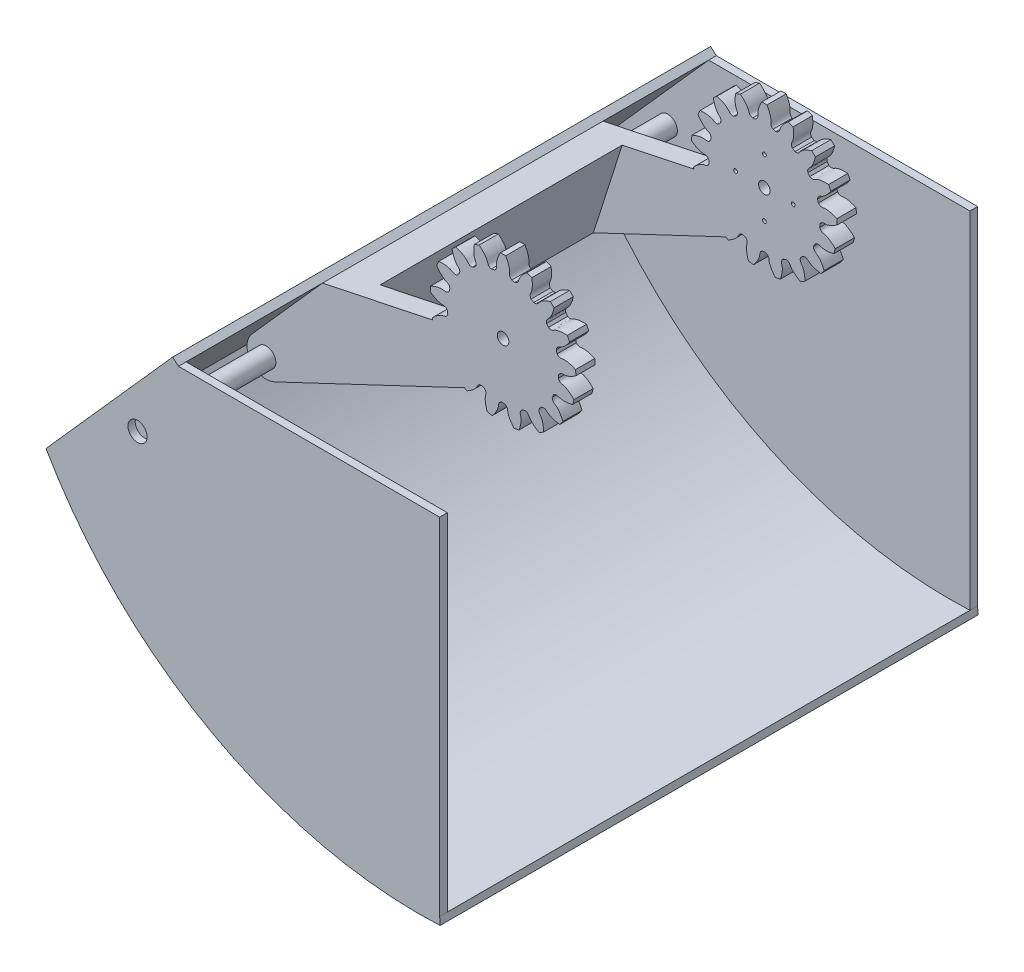
SolidWorks part; units mm, degrees
note: '?' marks a value the reader was unsure of.
ref_plane "前视基准面" through (0, 0, 0) normal (0, 0, 1) x (1, 0, 0)
ref_plane "上视基准面" through (0, 0, 0) normal (0, 1, 0) x (1, 0, 0)
ref_plane "右视基准面" through (0, 0, 0) normal (1, 0, 0) x (0, 0, -1)
sketch "草图1" plane through (0, 0, 0) normal (0, 0, 1) x (1, 0, 0)
  circle A0 centre (0, 0) radius 19
extrude "凸台-拉伸1" add sketch "草图1" along normal blind 5
ref_axis "基准轴1" through (0, 0, -1.5) along (0, 0, 1)?
sketch "草图2" plane through (0, 0, 0) normal (0, 0, 1) x (1, 0, 0)
  line L0 (0, 0) -> (0, 19) construction
  circle A0 centre (0, 0) radius 19 construction
  arc A1 (-2.2668, 14.3217) -> (-3.0598, 14.1735) centre (0, 0) ccw
  arc A2 (2.1781, 22.2607) -> (-10.0723, 19.9707) centre (0, 0) ccw
  spline S0 degree 3 poles (-2.2668, 14.3217) (-1.4942, 14.8276) (-1.7367, 15.4536) (-1.7089, 16.0896) (-1.7054, 16.1438) (-1.7004, 16.2043) (-1.6935, 16.271) (-1.6844, 16.344) (-1.673, 16.423) (-1.659, 16.5081) (-1.6421, 16.5993) (-1.6221, 16.6963) (-1.5988, 16.7991) (-1.5719, 16.9076) (-1.5411, 17.0218) (-1.5063, 17.1414) (-1.4672, 17.2665) (-1.4236, 17.3967) (-1.3753, 17.5321) (-1.3219, 17.6725) (-1.2634, 17.8177) (-1.1995, 17.9676) (-1.13, 18.1221) (-1.0547, 18.2808) (-0.9733, 18.4438) (-0.8858, 18.6107) (-0.7918, 18.7815) (-0.6913, 18.9559) (-0.584, 19.1337) (-0.4697, 19.3147) (-0.3483, 19.4988) (-0.2197, 19.6856) (-0.0836, 19.875) (0.0601, 20.0668) (0.2115, 20.2607) (0.3708, 20.4565) (0.5381, 20.654) (0.7135, 20.8528) (0.8973, 21.0529) (1.0893, 21.2538) (1.2899, 21.4553) (1.4991, 21.6573) (1.7927, 21.9296) (2.0214, 22.1293) (2.1781, 22.2607) knots 0 0 0 0 0.193883 0.199024 0.204851 0.211363 0.21856 0.226443 0.235011 0.244265 0.254205 0.264829 0.27614 0.288136 0.300817 0.314184 0.328236 0.342973 0.358397 0.374505 0.391299 0.408779 0.426944 0.445795 0.465331 0.485552 0.506459 0.528051 0.550329 0.573293 0.596941 0.621276 0.646296 0.672001 0.698392 0.725468 0.753229 0.781677 0.810809 0.840627 0.871131 0.90232 0.934195 1 1 1 1
  spline S1 degree 3 poles (-3.0598, 14.1735) (-3.9629, 14.3661) (-3.9629, 15.0375) (-4.2186, 15.6205) (-4.2414, 15.6698) (-4.268, 15.7243) (-4.2985, 15.7841) (-4.3333, 15.8488) (-4.3725, 15.9184) (-4.4163, 15.9927) (-4.465, 16.0716) (-4.5186, 16.1548) (-4.5776, 16.2423) (-4.6419, 16.3338) (-4.7118, 16.4291) (-4.7874, 16.5281) (-4.8691, 16.6306) (-4.9568, 16.7363) (-5.0508, 16.8451) (-5.1512, 16.9567) (-5.2583, 17.071) (-5.372, 17.1877) (-5.4926, 17.3066) (-5.6202, 17.4274) (-5.7549, 17.55) (-5.8969, 17.674) (-6.0462, 17.7993) (-6.2029, 17.9256) (-6.3672, 18.0526) (-6.5391, 18.1802) (-6.7188, 18.3079) (-6.9062, 18.4357) (-7.1016, 18.5632) (-7.3048, 18.6901) (-7.5161, 18.8162) (-7.7353, 18.9413) (-7.9627, 19.0649) (-8.1981, 19.187) (-8.4417, 19.3071) (-8.6934, 19.4251) (-8.9532, 19.5406) (-9.2212, 19.6534) (-9.5934, 19.8013) (-9.8788, 19.9048) (-10.0723, 19.9707) knots 0 0 0 0 0.193883 0.199024 0.204851 0.211363 0.21856 0.226443 0.235011 0.244265 0.254205 0.264829 0.27614 0.288136 0.300817 0.314184 0.328236 0.342973 0.358397 0.374505 0.391299 0.408779 0.426944 0.445795 0.465331 0.485552 0.506459 0.528051 0.550329 0.573293 0.596941 0.621276 0.646296 0.672001 0.698392 0.725468 0.753229 0.781677 0.810809 0.840627 0.871131 0.90232 0.934195 1 1 1 1
extrude "切除-拉伸1" cut sketch "草图2" along normal through all
pattern_circular "阵列(圆周)1" count 17 over 360 about axis through (0, 0, -1.5) along (0, 0, 1) of "切除-拉伸1"
sketch "草图3" plane through (0, 0, 0) normal (0, 0, 1) x (1, 0, 0)
  circle A0 centre (0, 0) radius 17 construction
  dimension "Dn" = 34
sketch "草图4" plane through (0, 0, 5) normal (0, 0, 1) x (1, 0, 0)
  circle A0 centre (0, 0) radius 1.5
  dimension "D1" = 3
extrude "切除-拉伸2" cut sketch "草图4" against normal up to next
sketch "草图5" plane through (0, 0, 5) normal (0, 0, 1) x (1, 0, 0)
  line L0 (-18.3355, -4.981) -> (-47, -11)
  line L1 (-47, -11) -> (-81.6624, -50)
  line L2 (-81.6624, -50) -> (-10.0568, -16.1202)
  line L3 (0, 0) -> (0, 43.3356) construction
  line L4 (-47, -11) -> (-47, -47.1311) construction
  arc A0 (-18.447, -4.5505) -> (-18.0795, -5.8421) centre (0, 0) ccw construction
  arc A1 (-18.3355, -4.981) -> (-18.0795, -5.8421) centre (0, 0) ccw
  arc A34 (-7.2873, 12.5358) -> (-7.9732, 12.1111) centre (0, 0) ccw
  arc A35 (-12.296, 14.4848) -> (-13.2884, 13.5801) centre (0, 0) ccw
  arc A36 (-11.3236, 9.0568) -> (-11.8098, 8.413) centre (0, 0) ccw
  arc A37 (-16.6982, 9.0649) -> (-17.2967, 7.8628) centre (0, 0) ccw
  arc A38 (-13.8307, 4.3546) -> (-14.0515, 3.5786) centre (0, 0) ccw
  arc A39 (-18.8452, 2.4207) -> (-18.9691, 1.0835) centre (0, 0) ccw
  arc A40 (-14.4698, -0.9356) -> (-14.3953, -1.739) centre (0, 0) ccw
  arc A41 (-18.447, -4.5505) -> (-18.0795, -5.8421) centre (0, 0) ccw
  arc A42 (-13.1547, -6.0996) -> (-12.7951, -6.8217) centre (0, 0) ccw
  arc A43 (-15.5575, -10.907) -> (-14.7483, -11.9787) centre (0, 0) ccw
  arc A44 (-10.063, -10.4397) -> (-9.4667, -10.9832) centre (0, 0) ccw
  arc A45 (-10.5669, -15.7905) -> (-9.4252, -16.4975) centre (0, 0) ccw
  arc A46 (-5.6122, -13.3699) -> (-4.8599, -13.6613) centre (0, 0) ccw
  arc A47 (-4.1491, -18.5414) -> (-2.8291, -18.7882) centre (0, 0) ccw
  arc A48 (-0.4034, -14.4944) -> (0.4033, -14.4944) centre (0, 0) ccw
  arc A49 (2.829, -18.7882) -> (4.149, -18.5415) centre (0, 0) ccw
  arc A50 (4.8598, -13.6614) -> (5.6121, -13.3699) centre (0, 0) ccw
  arc A51 (9.425, -16.4975) -> (10.5668, -15.7906) centre (0, 0) ccw
  arc A52 (9.4667, -10.9833) -> (10.0629, -10.4398) centre (0, 0) ccw
  arc A53 (14.7482, -11.9788) -> (15.5574, -10.9071) centre (0, 0) ccw
  arc A54 (12.795, -6.8219) -> (13.1546, -6.0997) centre (0, 0) ccw
  arc A55 (18.0795, -5.8422) -> (18.447, -4.5506) centre (0, 0) ccw
  arc A56 (14.3953, -1.7391) -> (14.4698, -0.9358) centre (0, 0) ccw
  arc A57 (18.9691, 1.0833) -> (18.8452, 2.4205) centre (0, 0) ccw
  arc A58 (14.0515, 3.5785) -> (13.8307, 4.3545) centre (0, 0) ccw
  arc A59 (17.2968, 7.8626) -> (16.6982, 9.0647) centre (0, 0) ccw
  arc A60 (11.8099, 8.4129) -> (11.3237, 9.0567) centre (0, 0) ccw
  arc A61 (13.2885, 13.58) -> (12.2961, 14.4847) centre (0, 0) ccw
  arc A62 (7.9733, 12.111) -> (7.2874, 12.5357) centre (0, 0) ccw
  arc A63 (7.4855, 17.4633) -> (6.2333, 17.9484) centre (0, 0) ccw
  arc A64 (3.0599, 14.1735) -> (2.2669, 14.3217) centre (0, 0) ccw
  arc A65 (0.6715, 18.9881) -> (-0.6714, 18.9881) centre (0, 0) ccw
  arc A66 (-2.2668, 14.3217) -> (-3.0598, 14.1735) centre (0, 0) ccw
  arc A67 (-6.2331, 17.9485) -> (-7.4853, 17.4634) centre (0, 0) ccw
  arc A76 (-13.1547, -6.0996) -> (-12.7951, -6.8217) centre (0, 0) ccw
  arc A77 (-15.5575, -10.907) -> (-14.7483, -11.9787) centre (0, 0) ccw
  arc A78 (-10.063, -10.4397) -> (-9.4667, -10.9832) centre (0, 0) ccw
  arc A79 (-10.5669, -15.7905) -> (-10.0568, -16.1202) centre (0, 0) ccw
  spline S36 degree 3 poles (677.1036, 740.5769) (-18.0035, -11.038) (-5.5387, 8.9839) (-9.5908, 13.056) (-9.6465, 13.1087) (-9.7101, 13.1654) (-9.7659, 13.2132) (-9.8515, 13.2836) (-9.9738, 13.3779) (-10.1405, 13.4964) (-10.3332, 13.622) (-10.5528, 13.753) (-10.7999, 13.8873) (-11.0751, 14.0229) (-11.3788, 14.1578) (-11.7114, 14.2899) (-35.5249, 22.663) (-89.1071, -59.695) (803.8496, 592.3248) knots -1.169641 -1.169641 -1.169641 -1.169641 0.661536 0.666677 0.679016 0.686213 0.694096 0.702664 0.721858 0.743793 0.76847 0.795889 0.82605 0.858952 0.894597 0.932984 0.974112 9.016656 9.016656 9.016656 9.016656 only from (-7.9732, 12.1111) to (-12.296, 14.4848)
  spline S37 degree 3 poles (-664.1971, -745.5759) (65.7577, 83.4356) (-19.5903, 36.6615) (-13.0986, 12.8048) (-12.9948, 12.4757) (-12.8865, 12.175) (-12.776, 11.9026) (-12.6652, 11.6581) (-12.572, 11.4724) (-12.4833, 11.3085) (-12.4149, 11.1906) (-12.3475, 11.082) (-12.3005, 11.0097) (-12.2557, 10.9435) (-12.2132, 10.8836) (-12.1626, 10.815) (-12.1153, 10.7546) (-8.4346, 6.3442) (12.6511, 16.9076) (-799.8323, -605.8265) knots -7.831656 -7.831656 -7.831656 -7.831656 0.046795 0.086552 0.123568 0.157842 0.189373 0.218163 0.244211 0.256207 0.278142 0.288082 0.297336 0.305904 0.313787 0.320984 0.333323 0.338464 2.169591 2.169591 2.169591 2.169591 only from (-13.2884, 13.5801) to (-11.3236, 9.0568)
  spline S38 degree 3 poles (363.8531, 935.1654) (-12.8004, -16.7963) (-8.41, 6.3765) (-13.6595, 8.7098) (-13.7305, 8.7388) (-13.8103, 8.7687) (-13.8796, 8.7931) (-13.9848, 8.8278) (-14.1329, 8.8716) (-14.3312, 8.9218) (-14.5563, 8.9693) (-14.8083, 9.0121) (-15.0872, 9.0481) (-15.3928, 9.0752) (-15.7248, 9.0913) (-16.0827, 9.0943) (-41.3128, 8.2995) (-61.5256, -87.8531) (535.5951, 842.7104) knots -1.169641 -1.169641 -1.169641 -1.169641 0.661536 0.666677 0.679016 0.686213 0.694096 0.702664 0.721858 0.743793 0.76847 0.795889 0.82605 0.858952 0.894597 0.932984 0.974112 9.016656 9.016656 9.016656 9.016656 only from (-11.8098, 8.413) to (-16.6982, 9.0649)
  spline S39 degree 3 poles (-350.0122, -935.1644) (31.1768, 101.5558) (-31.5111, 27.109) (-16.8397, 7.2083) (-16.624, 6.939) (-16.4145, 6.6977) (-16.213, 6.4836) (-16.0213, 6.2956) (-15.8674, 6.1562) (-15.7254, 6.0354) (-15.6191, 5.9501) (-15.517, 5.8732) (-15.447, 5.8227) (-15.3813, 5.7773) (-15.3201, 5.7367) (-15.2481, 5.6911) (-15.1822, 5.6518) (-10.1568, 2.8688) (5.6891, 20.3359) (-526.9716, -853.8492) knots -7.831656 -7.831656 -7.831656 -7.831656 0.046795 0.086552 0.123568 0.157842 0.189373 0.218163 0.244211 0.256207 0.278142 0.288082 0.297336 0.305904 0.313787 0.320984 0.333323 0.338464 2.169591 2.169591 2.169591 2.169591 only from (-17.2967, 7.8628) to (-13.8307, 4.3546)
  spline S40 degree 3 poles (1.4622, 1003.4547) (-5.8685, -20.2861) (-10.1456, 2.9078) (-15.8835, 3.1873) (-15.9602, 3.1886) (-16.0453, 3.1877) (-16.1188, 3.1854) (-16.2294, 3.1798) (-16.3834, 3.1671) (-16.5864, 3.1423) (-16.8135, 3.1053) (-17.0639, 3.0542) (-17.337, 2.987) (-17.6317, 2.9018) (-17.9471, 2.7969) (-18.2819, 2.6704) (-41.5212, -7.1848) (-25.6347, -104.1462) (195.0054, 979.2833) knots -1.169641 -1.169641 -1.169641 -1.169641 0.661536 0.666677 0.679016 0.686213 0.694096 0.702664 0.721858 0.743793 0.76847 0.795889 0.82605 0.858952 0.894597 0.932984 0.974112 9.016656 9.016656 9.016656 9.016656 only from (-14.0515, 3.5786) to (-18.8452, 2.4207)
  spline S41 degree 3 poles (11.4437, -998.4539) (-7.6147, 105.9603) (-39.1761, 13.8953) (-18.3065, 0.6384) (-18.0081, 0.4651) (-17.7255, 0.3158) (-17.4603, 0.189) (-17.2137, 0.0829) (-17.0198, 0.0085) (-16.8438, -0.0528) (-16.7138, -0.094) (-16.5908, -0.1288) (-16.5073, -0.1506) (-16.4297, -0.1692) (-16.3579, -0.1849) (-16.2743, -0.2015) (-16.1987, -0.2143) (-10.5073, -0.994) (-2.0413, 21.0178) (-182.9405, -986.5547) knots -7.831656 -7.831656 -7.831656 -7.831656 0.046795 0.086552 0.123568 0.157842 0.189373 0.218163 0.244211 0.256207 0.278142 0.288082 0.297336 0.305904 0.313787 0.320984 0.333323 0.338464 2.169591 2.169591 2.169591 2.169591 only from (-18.9691, 1.0835) to (-14.4698, -0.9356)
  spline S42 degree 3 poles (-361.1262, 936.2218) (1.856, -21.0361) (-10.5109, -0.9535) (-15.9623, -2.7657) (-16.0343, -2.7922) (-16.1134, -2.8238) (-16.181, -2.8525) (-16.2822, -2.8977) (-16.4211, -2.9651) (-16.6015, -3.0616) (-16.7999, -3.1781) (-17.0149, -3.3163) (-17.2453, -3.4776) (-17.4893, -3.6634) (-17.7455, -3.8752) (-18.012, -4.1141) (-36.1219, -21.6989) (13.7183, -106.3738) (-171.9208, 983.5986) knots -1.169641 -1.169641 -1.169641 -1.169641 0.661536 0.666677 0.679016 0.686213 0.694096 0.702664 0.721858 0.743793 0.76847 0.795889 0.82605 0.858952 0.894597 0.932984 0.974112 9.016656 9.016656 9.016656 9.016656 only from (-14.3953, -1.739) to (-18.447, -4.5505)
  spline S43 degree 3 poles (1105.7619, -2787.1089) (-45.1839, 188.8506) (-51.2232, 0.7287) (-17.3009, -6.0178) (-16.96, -6.0716) (-16.6426, -6.1087) (-16.3495, -6.1312) (-16.0813, -6.141) (-15.8735, -6.1403) (-15.6873, -6.1339) (-15.5512, -6.1253) (-15.424, -6.1133) (-15.3382, -6.1035) (-15.2591, -6.0929) (-15.1865, -6.0816) (-15.1025, -6.0669) (-15.0274, -6.0514) (-7.0466, -4.1537) (-10.5867, 43.3187) (564.5904, -2949.4471) knots -11.004981 -11.004981 -11.004981 -11.004981 0.046795 0.086552 0.123568 0.157842 0.189373 0.218163 0.244211 0.256207 0.278142 0.288082 0.297336 0.305904 0.313787 0.320984 0.333323 0.338464 2.960823 2.960823 2.960823 2.960823 only from (-18.0795, -5.8421) to (-13.1547, -6.0996)
  spline S44 degree 3 poles (-2013.5363, 2228.1044) (28.1899, -34.5548) (-7.5612, -3.12) (-13.8853, -8.3452) (-13.9428, -8.3959) (-14.0052, -8.454) (-14.0579, -8.5051) (-14.1359, -8.5838) (-14.2411, -8.6968) (-14.3744, -8.852) (-14.5173, -9.0323) (-14.668, -9.2388) (-14.8245, -9.4725) (-14.9849, -9.7339) (-15.1473, -10.0239) (-15.3095, -10.3429) (-30.0426, -42.4246) (126.9734, -149.1625) (-1560.4003, 2560.4234) knots -1.96086 -1.96086 -1.96086 -1.96086 0.661536 0.666677 0.679016 0.686213 0.694096 0.702664 0.721858 0.743793 0.76847 0.795889 0.82605 0.858952 0.894597 0.932984 0.974112 12.253625 12.253625 12.253625 12.253625 only from (-12.7951, -6.8217) to (-15.5575, -10.907)
  spline S45 degree 3 poles (2037.9122, -2199.4543) (-110.3534, 159.7757) (-48.0274, -17.8245) (-13.9588, -11.8613) (-13.6215, -11.7882) (-13.3121, -11.7082) (-13.0306, -11.6233) (-12.7769, -11.5355) (-12.5835, -11.4598) (-12.4121, -11.3866) (-12.2883, -11.3295) (-12.174, -11.2723) (-12.0976, -11.2322) (-12.0277, -11.1936) (-11.964, -11.1569) (-11.8911, -11.1128) (-11.8266, -11.0713) (-5.0703, -6.4188) (-25.5203, 36.5692) (1591.928, -2546.324) knots -11.004981 -11.004981 -11.004981 -11.004981 0.046795 0.086552 0.123568 0.157842 0.189373 0.218163 0.244211 0.256207 0.278142 0.288082 0.297336 0.305904 0.313787 0.320984 0.333323 0.338464 2.960823 2.960823 2.960823 2.960823 only from (-14.7483, -11.9787) to (-10.063, -10.4397)
  spline S46 degree 3 poles (-2682.4508, 1350.2723) (38.769, -22.038) (-5.9235, -5.6408) (-9.933, -12.7976) (-9.9684, -12.8657) (-10.0055, -12.9423) (-10.0362, -13.0091) (-10.0805, -13.1106) (-10.1378, -13.2541) (-10.2061, -13.4468) (-10.2742, -13.6666) (-10.34, -13.9136) (-10.4016, -14.188) (-10.4567, -14.4898) (-10.5034, -14.8189) (-10.5394, -15.175) (-12.6884, -50.4124) (172.2828, -93.2219) (-2379.9615, 1823.8421) knots -1.96086 -1.96086 -1.96086 -1.96086 0.661536 0.666677 0.679016 0.686213 0.694096 0.702664 0.721858 0.743793 0.76847 0.795889 0.82605 0.858952 0.894597 0.932984 0.974112 12.253625 12.253625 12.253625 12.253625 only from (-9.4667, -10.9832) to (-10.5669, -15.7905)
  spline S47 degree 3 poles (898.8801, -434.8052) (-98.246, 40.4142) (-29.9008, -28.8754) (-8.7314, -16.1028) (-8.4432, -15.9128) (-8.1837, -15.7265) (-7.9519, -15.5456) (-7.747, -15.3721) (-7.594, -15.2317) (-7.4606, -15.1015) (-7.3659, -15.0035) (-7.2799, -14.9089) (-7.2232, -14.8439) (-7.1719, -14.7827) (-7.1258, -14.7254) (-7.0737, -14.658) (-7.0286, -14.596) (-3.7937, -9.8488) (-19.7243, 7.5412) (801.584, -603.5069) knots -7.831656 -7.831656 -7.831656 -7.831656 0.046795 0.086552 0.123568 0.157842 0.189373 0.218163 0.244211 0.256207 0.278142 0.288082 0.297336 0.305904 0.313787 0.320984 0.333323 0.338464 2.169591 2.169591 2.169591 2.169591 only from (-9.4252, -16.4975) to (-5.6122, -13.3699)
  spline S48 degree 3 poles (-999.0392, 94.0431) (19.6581, -7.7152) (-3.8315, -9.834) (-4.6392, -15.5216) (-4.6476, -15.5979) (-4.6546, -15.6828) (-4.6591, -15.7561) (-4.6637, -15.8668) (-4.6653, -16.0212) (-4.6593, -16.2257) (-4.6434, -16.4552) (-4.6156, -16.7093) (-4.5739, -16.9874) (-4.5163, -17.2888) (-4.4409, -17.6124) (-4.3459, -17.9575) (3.3231, -42.007) (101.3366, -35.1348) (-957.113, 284.5304) knots -1.169641 -1.169641 -1.169641 -1.169641 0.661536 0.666677 0.679016 0.686213 0.694096 0.702664 0.721858 0.743793 0.76847 0.795889 0.82605 0.858952 0.894597 0.932984 0.974112 9.016656 9.016656 9.016656 9.016656 only from (-4.8599, -13.6613) to (-4.1491, -18.5414)
  spline S49 degree 3 poles (995.2505, -80.7309) (-106.2109, 2.1946) (-17.4507, -37.7269) (-2.3248, -18.1695) (-2.1247, -17.8883) (-1.95, -17.6208) (-1.7992, -17.3684) (-1.6708, -17.1326) (-1.5789, -16.9464) (-1.5015, -16.7768) (-1.4486, -16.6512) (-1.4026, -16.5319) (-1.3732, -16.4508) (-1.3475, -16.3752) (-1.3252, -16.3052) (-1.301, -16.2235) (-1.2813, -16.1494) (0.0202, -10.5542) (-21.1165, -0.0933) (965.4666, -273.1879) knots -7.831656 -7.831656 -7.831656 -7.831656 0.046795 0.086552 0.123568 0.157842 0.189373 0.218163 0.244211 0.256207 0.278142 0.288082 0.297336 0.305904 0.313787 0.320984 0.333323 0.338464 2.169591 2.169591 2.169591 2.169591 only from (-2.8291, -18.7882) to (-0.4034, -14.4944)
  spline S50 degree 3 poles (-965.5486, -273.202) (21.1176, -0.0929) (-0.0204, -10.554) (1.2811, -16.1494) (1.3008, -16.2235) (1.325, -16.3052) (1.3473, -16.3752) (1.383, -16.4801) (1.4373, -16.6247) (1.5167, -16.8131) (1.6144, -17.0214) (1.7322, -17.2483) (1.8715, -17.4926) (2.0341, -17.7528) (2.2213, -18.0274) (2.4346, -18.3148) (18.2734, -37.9699) (107.1857, 3.8448) (-995.2656, -80.4324) knots -1.169641 -1.169641 -1.169641 -1.169641 0.661536 0.666677 0.679016 0.686213 0.694096 0.702664 0.721858 0.743793 0.76847 0.795889 0.82605 0.858952 0.894597 0.932984 0.974112 9.016656 9.016656 9.016656 9.016656 only from (0.4033, -14.4944) to (2.829, -18.7882)
  spline S51 degree 3 poles (957.2068, 284.2467) (-99.8315, -36.3214) (-2.6438, -41.4832) (4.3958, -17.7824) (4.4808, -17.4479) (4.5471, -17.1353) (4.5965, -16.8455) (4.631, -16.5793) (4.6495, -16.3724) (4.6603, -16.1863) (4.6643, -16.05) (4.6641, -15.9222) (4.6623, -15.836) (4.6589, -15.7562) (4.6544, -15.6828) (4.6475, -15.5979) (4.6391, -15.5217) (3.8315, -9.8342) (-19.6569, -7.7152) (998.9577, 94.0267) knots -7.831656 -7.831656 -7.831656 -7.831656 0.046795 0.086552 0.123568 0.157842 0.189373 0.218163 0.244211 0.256207 0.278142 0.288082 0.297336 0.305904 0.313787 0.320984 0.333323 0.338464 2.169591 2.169591 2.169591 2.169591 only from (4.149, -18.5415) to (4.8598, -13.6614)
  spline S52 degree 3 poles (-801.6553, -603.5497) (19.7252, 7.5419) (3.7936, -9.8487) (7.0284, -14.596) (7.0736, -14.658) (7.1257, -14.7255) (7.1717, -14.7827) (7.2429, -14.8676) (7.3457, -14.9828) (7.4879, -15.1299) (7.6543, -15.2888) (7.846, -15.4579) (8.0642, -15.6353) (8.3098, -15.8192) (8.5835, -16.0076) (8.8862, -16.1986) (30.7558, -28.8048) (98.5588, 42.3051) (-899.002, -434.5324) knots -1.169641 -1.169641 -1.169641 -1.169641 0.661536 0.666677 0.679016 0.686213 0.694096 0.702664 0.721858 0.743793 0.76847 0.795889 0.82605 0.858952 0.894597 0.932984 0.974112 9.016656 9.016656 9.016656 9.016656 only from (5.6121, -13.3699) to (9.425, -16.4975)
  spline S53 degree 3 poles (789.8871, 610.8351) (-79.9693, -69.932) (12.5202, -39.637) (10.5227, -14.9936) (10.4811, -14.651) (10.43, -14.3356) (10.3714, -14.0475) (10.3074, -13.7868) (10.2499, -13.5872) (10.1928, -13.4098) (10.1473, -13.2813) (10.1009, -13.1622) (10.068, -13.0824) (10.0361, -13.0092) (10.0054, -12.9424) (9.9683, -12.8657) (9.9329, -12.7977) (7.1253, -7.786) (-15.5424, -14.2951) (897.534, 448.5424) knots -7.831656 -7.831656 -7.831656 -7.831656 0.046795 0.086552 0.123568 0.157842 0.189373 0.218163 0.244211 0.256207 0.278142 0.288082 0.297336 0.305904 0.313787 0.320984 0.333323 0.338464 2.169591 2.169591 2.169591 2.169591 only from (10.5668, -15.7906) to (9.4667, -10.9833)
  spline S54 degree 3 poles (-529.494, -852.3846) (15.6687, 14.1582) (7.0952, -7.8132) (11.8265, -11.0714) (11.891, -11.1129) (11.9639, -11.157) (12.0276, -11.1937) (12.1246, -11.2472) (12.2621, -11.3175) (12.4478, -11.4033) (12.6603, -11.4913) (12.9002, -11.5797) (13.1678, -11.6663) (13.4632, -11.7491) (13.7865, -11.8259) (14.1378, -11.8946) (39.0844, -15.7494) (76.621, 75.0519) (-681.3232, -729.9463) knots -1.169641 -1.169641 -1.169641 -1.169641 0.661536 0.666677 0.679016 0.686213 0.694096 0.702664 0.721858 0.743793 0.76847 0.795889 0.82605 0.858952 0.894597 0.932984 0.974112 9.016656 9.016656 9.016656 9.016656 only from (10.0629, -10.4398) to (14.7482, -11.9788)
  spline S55 degree 3 poles (515.8886, 854.9269) (-49.3068, -94.0979) (25.9933, -32.4376) (15.2285, -10.1799) (15.0659, -9.8755) (14.9043, -9.5998) (14.7456, -9.3523) (14.5917, -9.1323) (14.466, -8.967) (14.3487, -8.8222) (14.2598, -8.7188) (14.1736, -8.6245) (14.1141, -8.562) (14.0579, -8.5052) (14.0051, -8.4541) (13.9428, -8.396) (13.8852, -8.3453) (9.4567, -4.6863) (-9.3289, -18.9443) (674.8933, 742.48) knots -7.831656 -7.831656 -7.831656 -7.831656 0.046795 0.086552 0.123568 0.157842 0.189373 0.218163 0.244211 0.256207 0.278142 0.288082 0.297336 0.305904 0.313787 0.320984 0.333323 0.338464 2.169591 2.169591 2.169591 2.169591 only from (15.5574, -10.9071) to (12.795, -6.8219)
  spline S56 degree 3 poles (-185.8216, -986.1003) (9.4961, 18.8623) (9.4385, -4.7226) (15.0274, -6.0516) (15.1025, -6.067) (15.1864, -6.0817) (15.259, -6.093) (15.3688, -6.1078) (15.5224, -6.1237) (15.7265, -6.1366) (15.9566, -6.1419) (16.2122, -6.1377) (16.4929, -6.1218) (16.7983, -6.0922) (17.1276, -6.047) (17.4799, -5.9843) (42.1344, -0.567) (44.3351, 97.6625) (-371.6279, -926.777) knots -1.169641 -1.169641 -1.169641 -1.169641 0.661536 0.666677 0.679016 0.686213 0.694096 0.702664 0.721858 0.743793 0.76847 0.795889 0.82605 0.858952 0.894597 0.932984 0.974112 9.016656 9.016656 9.016656 9.016656 only from (13.1546, -6.0997) to (18.0795, -5.8422)
  spline S57 degree 3 poles (172.2166, 983.5561) (-11.9851, -105.5554) (35.9558, -20.8573) (17.8775, -3.9913) (17.616, -3.7661) (17.3657, -3.5675) (17.1283, -3.3941) (16.9054, -3.2445) (16.7284, -3.1358) (16.5667, -3.0431) (16.4465, -2.9788) (16.332, -2.922) (16.2539, -2.8852) (16.181, -2.8526) (16.1133, -2.824) (16.0342, -2.7923) (15.9622, -2.7659) (10.511, -0.9537) (-1.8555, -21.035) (361.1045, 936.1415) knots -7.831656 -7.831656 -7.831656 -7.831656 0.046795 0.086552 0.123568 0.157842 0.189373 0.218163 0.244211 0.256207 0.278142 0.288082 0.297336 0.305904 0.313787 0.320984 0.333323 0.338464 2.169591 2.169591 2.169591 2.169591 only from (18.447, -4.5506) to (14.3953, -1.7391)
  spline S58 degree 3 poles (182.947, -986.6376) (2.041, 21.019) (10.5071, -0.9941) (16.1987, -0.2144) (16.2743, -0.2016) (16.3579, -0.1851) (16.4297, -0.1693) (16.5374, -0.1435) (16.6864, -0.1028) (16.8814, -0.0411) (17.0978, 0.037) (17.3346, 0.1333) (17.5907, 0.2496) (17.8647, 0.3874) (18.1554, 0.5485) (18.4613, 0.7343) (39.494, 14.692) (6.0614, 107.0833) (-11.7423, -998.4413) knots -1.169641 -1.169641 -1.169641 -1.169641 0.661536 0.666677 0.679016 0.686213 0.694096 0.702664 0.721858 0.743793 0.76847 0.795889 0.82605 0.858952 0.894597 0.932984 0.974112 9.016656 9.016656 9.016656 9.016656 only from (14.4698, -0.9358) to (18.9691, 1.0833)
  spline S59 degree 3 poles (-194.7142, 979.3505) (26.9552, -102.757) (41.0623, -6.4601) (18.1121, 2.7363) (17.7869, 2.8518) (17.4817, 2.9466) (17.1977, 3.0226) (16.9358, 3.0815) (16.7315, 3.119) (16.5473, 3.147) (16.4119, 3.1635) (16.2847, 3.1751) (16.1986, 3.1812) (16.1188, 3.1853) (16.0454, 3.1875) (15.9602, 3.1885) (15.8835, 3.1871) (10.1457, 2.9077) (5.8685, -20.2849) (-1.4534, 1003.372) knots -7.831656 -7.831656 -7.831656 -7.831656 0.046795 0.086552 0.123568 0.157842 0.189373 0.218163 0.244211 0.256207 0.278142 0.288082 0.297336 0.305904 0.313787 0.320984 0.333323 0.338464 2.169591 2.169591 2.169591 2.169591 only from (18.8452, 2.4205) to (14.0515, 3.5785)
  spline S60 degree 3 poles (527.0076, -853.9241) (-5.6898, 20.3369) (10.1567, 2.8687) (15.1823, 5.6517) (15.2482, 5.6909) (15.3201, 5.7366) (15.3814, 5.7772) (15.4725, 5.8402) (15.5967, 5.932) (15.7562, 6.0599) (15.9298, 6.2109) (16.1159, 6.3863) (16.3126, 6.5872) (16.5184, 6.8147) (16.7313, 7.0699) (16.9494, 7.3537) (31.5197, 27.9668) (-33.0308, 102.0418) (349.7293, -935.2606) knots -1.169641 -1.169641 -1.169641 -1.169641 0.661536 0.666677 0.679016 0.686213 0.694096 0.702664 0.721858 0.743793 0.76847 0.795889 0.82605 0.858952 0.894597 0.932984 0.974112 9.016656 9.016656 9.016656 9.016656 only from (13.8307, 4.3545) to (17.2968, 7.8626)
  spline S61 degree 3 poles (-535.3478, 842.8783) (62.2551, -86.0807) (40.6231, 8.8096) (15.9006, 9.0944) (15.5556, 9.0846) (15.2368, 9.0628) (14.9445, 9.031) (14.679, 8.9913) (14.475, 8.9525) (14.2931, 8.912) (14.1609, 8.8786) (14.038, 8.8434) (13.9556, 8.818) (13.8797, 8.793) (13.8104, 8.7686) (13.7306, 8.7386) (13.6596, 8.7097) (8.4102, 6.3765) (12.8, -16.7951) (-363.815, 935.0915) knots -7.831656 -7.831656 -7.831656 -7.831656 0.046795 0.086552 0.123568 0.157842 0.189373 0.218163 0.244211 0.256207 0.278142 0.288082 0.297336 0.305904 0.313787 0.320984 0.333323 0.338464 2.169591 2.169591 2.169591 2.169591 only from (16.6982, 9.0647) to (11.8099, 8.4129)
  spline S62 degree 3 poles (799.8929, -605.8834) (-12.6521, 16.9082) (8.4346, 6.344) (12.1154, 10.7545) (12.1627, 10.8149) (12.2133, 10.8835) (12.2558, 10.9434) (12.3179, 11.0351) (12.4006, 11.1656) (12.5032, 11.3425) (12.6105, 11.546) (12.7206, 11.7768) (12.8315, 12.0352) (12.9412, 12.3217) (13.0475, 12.6366) (13.1484, 12.98) (19.2885, 37.4645) (-67.6621, 83.2191) (663.9679, -745.7677) knots -1.169641 -1.169641 -1.169641 -1.169641 0.661536 0.666677 0.679016 0.686213 0.694096 0.702664 0.721858 0.743793 0.76847 0.795889 0.82605 0.858952 0.894597 0.932984 0.974112 9.016656 9.016656 9.016656 9.016656 only from (11.3237, 9.0567) to (13.2885, 13.58)
  spline S63 degree 3 poles (-803.6797, 592.5707) (89.147, -57.7787) (34.6975, 22.8894) (11.5416, 14.2242) (11.2234, 14.0905) (10.934, 13.9549) (10.673, 13.8197) (10.4397, 13.6869) (10.2635, 13.5769) (10.1085, 13.4735) (9.9973, 13.3945) (9.8954, 13.3173) (9.8277, 13.2639) (9.7661, 13.2131) (9.7102, 13.1653) (9.6467, 13.1086) (9.5909, 13.056) (5.5389, 8.984) (18.0027, -11.0371) (-677.0414, 740.5217) knots -7.831656 -7.831656 -7.831656 -7.831656 0.046795 0.086552 0.123568 0.157842 0.189373 0.218163 0.244211 0.256207 0.278142 0.288082 0.297336 0.305904 0.313787 0.320984 0.333323 0.338464 2.169591 2.169591 2.169591 2.169591 only from (12.2961, 14.4847) to (7.9733, 12.111)
  spline S64 degree 3 poles (964.7483, -276.0148) (-17.9057, 11.196) (5.5733, 8.9625) (7.4123, 14.4049) (7.4346, 14.4783) (7.457, 14.5605) (7.4749, 14.6317) (7.4998, 14.7397) (7.5298, 14.8912) (7.5614, 15.0933) (7.588, 15.3218) (7.6074, 15.5767) (7.6174, 15.8577) (7.6162, 16.1645) (7.6016, 16.4965) (7.5716, 16.8532) (4.4523, 41.9024) (-93.1552, 53.1571) (888.534, -455.5548) knots -1.169641 -1.169641 -1.169641 -1.169641 0.661536 0.666677 0.679016 0.686213 0.694096 0.702664 0.721858 0.743793 0.76847 0.795889 0.82605 0.858952 0.894597 0.932984 0.974112 9.016656 9.016656 9.016656 9.016656 only from (7.2874, 12.5357) to (7.4855, 17.4633)
  spline S65 degree 3 poles (-963.4703, 262.2331) (103.9992, -21.6734) (24.0859, 33.878) (5.6238, 17.433) (5.3755, 17.1933) (5.1546, 16.9624) (4.96, 16.742) (4.7905, 16.5339) (4.6659, 16.3677) (4.5587, 16.2152) (4.4836, 16.1015) (4.4165, 15.9927) (4.3726, 15.9184) (4.3334, 15.8488) (4.2987, 15.784) (4.2599, 15.7082) (4.2269, 15.6389) (1.9194, 10.3782) (20.7741, -3.7884) (-898.8296, 445.9404) knots -7.831656 -7.831656 -7.831656 -7.831656 0.046795 0.086552 0.123568 0.157842 0.189373 0.218163 0.244211 0.256207 0.278142 0.288082 0.297336 0.305904 0.313787 0.320984 0.333323 0.338464 2.169591 2.169591 2.169591 2.169591 only from (6.2333, 17.9484) to (3.0599, 14.1735)
  spline S66 degree 3 poles (999.309, 91.1311) (-20.741, 3.9717) (1.9593, 10.3706) (1.7081, 16.1098) (1.7024, 16.1863) (1.6936, 16.271) (1.6846, 16.344) (1.6688, 16.4536) (1.642, 16.6057) (1.5985, 16.8055) (1.5407, 17.0283) (1.4667, 17.2729) (1.3746, 17.5386) (1.2626, 17.8243) (1.129, 18.1286) (0.9722, 18.4503) (-10.9853, 40.6812) (-106.0672, 15.916) (993.0987, -103.8167) knots -1.169641 -1.169641 -1.169641 -1.169641 0.661536 0.666677 0.679016 0.686213 0.694096 0.702664 0.721858 0.743793 0.76847 0.795889 0.82605 0.858952 0.894597 0.932984 0.974112 9.016656 9.016656 9.016656 9.016656 only from (2.2669, 14.3217) to (0.6715, 18.9881)
  spline S67 degree 3 poles (-993.1388, -103.5205) (104.8057, 17.359) (10.2213, 40.2911) (-1.0535, 18.2874) (-1.1985, 17.9742) (-1.321, 17.679) (-1.4229, 17.4032) (-1.5057, 17.1479) (-1.5619, 16.9479) (-1.6068, 16.767) (-1.6357, 16.6338) (-1.659, 16.5081) (-1.673, 16.423) (-1.6844, 16.344) (-1.6935, 16.271) (-1.7022, 16.1863) (-1.708, 16.1098) (-1.9592, 10.3708) (20.7398, 3.9719) (-999.2259, 91.1323) knots -7.831656 -7.831656 -7.831656 -7.831656 0.046795 0.086552 0.123568 0.157842 0.189373 0.218163 0.244211 0.256207 0.278142 0.288082 0.297336 0.305904 0.313787 0.320984 0.333323 0.338464 2.169591 2.169591 2.169591 2.169591 only from (-0.6714, 18.9881) to (-2.2668, 14.3217)
  spline S68 degree 3 poles (898.9075, 445.9693) (-20.7751, -3.789) (-1.9193, 10.3781) (-4.2268, 15.639) (-4.2597, 15.7082) (-4.2985, 15.7841) (-4.3333, 15.8488) (-4.3877, 15.9453) (-4.4676, 16.0775) (-4.5803, 16.2482) (-4.7146, 16.4349) (-4.8721, 16.6364) (-5.0539, 16.8508) (-5.2615, 17.0767) (-5.496, 17.3122) (-5.7585, 17.5556) (-24.9392, 33.9657) (-104.6542, -23.4747) (963.5399, 261.9424) knots -1.169641 -1.169641 -1.169641 -1.169641 0.661536 0.666677 0.679016 0.686213 0.694096 0.702664 0.721858 0.743793 0.76847 0.795889 0.82605 0.858952 0.894597 0.932984 0.974112 9.016656 9.016656 9.016656 9.016656 only from (-3.0598, 14.1735) to (-6.2331, 17.9485)
  spline S69 degree 3 poles (-888.6784, -455.2931) (91.4576, 54.047) (-5.0238, 41.2627) (-7.5885, 16.6719) (-7.6106, 16.3275) (-7.6182, 16.008) (-7.6136, 15.714) (-7.5986, 15.446) (-7.5787, 15.2393) (-7.5552, 15.0544) (-7.5341, 14.9197) (-7.5104, 14.7941) (-7.4927, 14.7097) (-7.4748, 14.6318) (-7.4569, 14.5605) (-7.4345, 14.4783) (-7.4122, 14.405) (-5.5733, 8.9627) (17.9045, 11.1957) (-964.6712, -275.9837) knots -7.831656 -7.831656 -7.831656 -7.831656 0.046795 0.086552 0.123568 0.157842 0.189373 0.218163 0.244211 0.256207 0.278142 0.288082 0.297336 0.305904 0.313787 0.320984 0.333323 0.338464 2.169591 2.169591 2.169591 2.169591 only from (-7.4853, 17.4634) to (-7.2873, 12.5358)
  spline S77 degree 3 poles (-18.0795, -5.8421) (-17.939, -5.8794) (-17.6776, -5.9429) (-17.3009, -6.0178) (-16.96, -6.0716) (-16.6426, -6.1087) (-16.3495, -6.1312) (-16.0813, -6.141) (-15.8735, -6.1403) (-15.6873, -6.1339) (-15.5512, -6.1253) (-15.424, -6.1133) (-15.3382, -6.1035) (-15.2591, -6.0929) (-15.1865, -6.0816) (-15.1025, -6.0669) (-15.0274, -6.0514) (-14.3884, -5.8995) (-13.8526, -5.4949) (-13.1547, -6.0996) knots 0 0 0 0 0.046795 0.086552 0.123568 0.157842 0.189373 0.218163 0.244211 0.256207 0.278142 0.288082 0.297336 0.305904 0.313787 0.320984 0.333323 0.338464 0.532347 0.532347 0.532347 0.532347
  spline S78 degree 3 poles (-12.7951, -6.8217) (-12.7331, -7.7431) (-13.3789, -7.9269) (-13.8853, -8.3452) (-13.9428, -8.3959) (-14.0052, -8.454) (-14.0579, -8.5051) (-14.1359, -8.5838) (-14.2411, -8.6968) (-14.3744, -8.852) (-14.5173, -9.0323) (-14.668, -9.2388) (-14.8245, -9.4725) (-14.9849, -9.7339) (-15.1473, -10.0239) (-15.3095, -10.3429) (-15.4463, -10.6406) (-15.5272, -10.8325) (-15.5575, -10.907) knots 0.467653 0.467653 0.467653 0.467653 0.661536 0.666677 0.679016 0.686213 0.694096 0.702664 0.721858 0.743793 0.76847 0.795889 0.82605 0.858952 0.894597 0.932984 0.974112 1 1 1 1
  spline S79 degree 3 poles (-14.7483, -11.9787) (-14.6037, -11.9627) (-14.337, -11.9275) (-13.9588, -11.8613) (-13.6215, -11.7882) (-13.3121, -11.7082) (-13.0306, -11.6233) (-12.7769, -11.5355) (-12.5835, -11.4598) (-12.4121, -11.3866) (-12.2883, -11.3295) (-12.174, -11.2723) (-12.0976, -11.2322) (-12.0277, -11.1936) (-11.964, -11.1569) (-11.8911, -11.1128) (-11.8266, -11.0713) (-11.2857, -10.6988) (-10.9322, -10.128) (-10.063, -10.4397) knots 0 0 0 0 0.046795 0.086552 0.123568 0.157842 0.189373 0.218163 0.244211 0.256207 0.278142 0.288082 0.297336 0.305904 0.313787 0.320984 0.333323 0.338464 0.532347 0.532347 0.532347 0.532347
  spline S80 degree 3 poles (-9.4667, -10.9832) (-9.0762, -11.82) (-9.612, -12.2246) (-9.933, -12.7976) (-9.9684, -12.8657) (-10.0055, -12.9423) (-10.0362, -13.0091) (-10.0805, -13.1106) (-10.1378, -13.2541) (-10.2061, -13.4468) (-10.2742, -13.6666) (-10.34, -13.9136) (-10.4016, -14.188) (-10.4567, -14.4898) (-10.5034, -14.8189) (-10.5394, -15.175) (-10.5594, -15.5019) (-10.5655, -15.7101) (-10.5669, -15.7905) knots 0.467653 0.467653 0.467653 0.467653 0.661536 0.666677 0.679016 0.686213 0.694096 0.702664 0.721858 0.743793 0.76847 0.795889 0.82605 0.858952 0.894597 0.932984 0.974112 1 1 1 1
  dimension "D1" = 47
  dimension "D2" = 41.63
  dimension "D3" = 11
  dimension "D5" = 50
  dimension "D6" = 28.6645
  dimension "D7" = 79.2161
  dimension "D4" = 0
extrude "凸台-拉伸2" add sketch "草图5" against normal blind 5
fillet "圆角1" radius 5 1 edges at (-81.6624, -50, 2.5)
sketch "草图6" plane through (0, 0, 5) normal (0, 0, 1) x (1, 0, 0)
  circle A0 centre (-61.6347, -34.9926) radius 2.5
  dimension "D1" = 5
extrude "凸台-拉伸3" add sketch "草图6" along normal blind 31.5 and the other way blind 36.5
ref_plane "基准面1" through (0, 0, -31.5) normal (0, 0, -1) x (-1, 0, 0)
mirror "镜向3" about plane through (0, 0, -31.5) normal (0, 0, -1) of bodies 112
sketch "草图12" plane through (0, 0, 0) normal (0, 0, -1) x (-1, 0, 0)
  line L1 (47, -11) -> (37, -8.9002)
  line L2 (47, -11) -> (65.3719, -31.671) construction
  line L3 (47, -11) -> (65.3719, -31.671)
  line L5 (18.3355, -4.981) -> (47, -11) construction
  line L6 (37, -8.9002) -> (44.4963, -32.4151)
  line L7 (59.4963, -39.5122) -> (10.0568, -16.1202) construction
  line L8 (44.4963, -32.4151) -> (59.4963, -39.5122)
  arc A0 (59.4963, -39.5122) -> (65.3719, -31.671) centre (61.6347, -34.9926) ccw construction
  arc A1 (59.4963, -39.5122) -> (65.3719, -31.671) centre (61.6347, -34.9926) ccw
  dimension "D1" = 10
  dimension "D2" = 15
extrude "凸台-拉伸6" add sketch "草图12" along normal up to surface (63 mm away)
sketch "草图7" plane through (0, 0, 36.5) normal (0, 0, 1) x (1, 0, 0)
  line L0 (-51, -15) -> (17, -15)
  line L1 (17, -15) -> (17, -105)
  line L2 (-51, -15) -> (-83, -51)
  arc A0 (-83, -51) -> (17, -105) centre (11.7524, 4.8748) ccw
  dimension "D3" = 110
  dimension "D1" = 17
  dimension "D2" = 15
  dimension "D4" = 100
  dimension "D5" = 68
  dimension "D6" = 36
  dimension "D7" = 90
extrude "凸台-拉伸4" add sketch "草图7" along normal blind 2
mirror "镜向4" about plane through (0, 0, -31.5) normal (0, 0, -1) of bodies 116
sketch "草图8" plane through (0, 0, 38.5) normal (0, 0, 1) x (1, 0, 0)
  line L0 (-51, -15) -> (-83, -51) construction
  line L1 (-51, -15) -> (-83, -51)
  arc A0 (-83, -51) -> (17, -105) centre (11.7524, 4.8748) ccw construction
  arc A1 (-83, -51) -> (17, -105) centre (11.7524, 4.8748) ccw
extrude "拉伸-薄壁1" add sketch "草图8" against normal up to surface (140 mm away) thin up to face at (-26.8785, -49.9787, -101.5) thin type one direction wall 2
sketch "草图13" plane through (-22.5362, 20.0322, 0) normal (-0.7474, 0.6644, 0) x (0, 0, 1)
  line L0 (-101.5, -45.0937) -> (38.5, -45.0937) construction
  line L1 (-31.5, -45.0937) -> (-31.5, -56.229) construction
  circle A0 centre (-56.5, -51.0937) radius 2.5
  circle A1 centre (-6.5, -51.0937) radius 2.5
  dimension "D1" = 5
  dimension "D2" = 5
  dimension "D3" = 6
  dimension "D4" = 6
  dimension "D5" = 25
  dimension "D6" = 25
extrude "切除-拉伸3" cut sketch "草图13" against normal blind 10
sketch "草图14" plane through (0, 0, 38.5) normal (0, 0, 1) x (1, 0, 0)
  circle A0 centre (-61.6347, -34.9926) radius 2.5 construction
  circle A1 centre (-61.6347, -34.9926) radius 2.5
extrude "切除-拉伸5" cut sketch "草图14" against normal blind 1.9
sketch "草图16" plane through (0, 0, -101.5) normal (0, 0, -1) x (-1, 0, 0)
  circle A0 centre (61.6347, -34.9926) radius 2.5 construction
  circle A1 centre (61.6347, -34.9926) radius 2.5
extrude "切除-拉伸7" cut sketch "草图16" against normal blind 1.9
sketch "草图17" plane through (0, 0, 38.5) normal (0, 0, 1) x (1, 0, 0)
  circle A0 centre (-61.6347, -34.9926) radius 2.5 construction
  circle A1 centre (-61.6347, -34.9926) radius 2.5
split "分割1" trim tools "草图17" bodies to split 124 resulting bodies 125 126 127
other "保存实体1"
sketch "草图18" plane through (0, 0, -68) normal (0, 0, -1) x (-1, 0, 0)
  line L0 (0, 16.7673) -> (0, -14.4484) construction
  line L1 (-14.4458, 0) -> (14.0932, 0) construction
  circle A0 centre (-7.5, 0) radius 0.5
  circle A1 centre (0, 7.5) radius 0.5
  circle A2 centre (7.5, 0) radius 0.5
  circle A3 centre (0, -7.5) radius 0.5
  dimension "D5" = 1
  dimension "D6" = 1
  dimension "D7" = 1
  dimension "D8" = 1
  dimension "D1" = 7.5
  dimension "D2" = 7.5
  dimension "D3" = 7.5
  dimension "D4" = 7.5
extrude "切除-拉伸8" cut sketch "草图18" against normal up to next (5 mm away)
